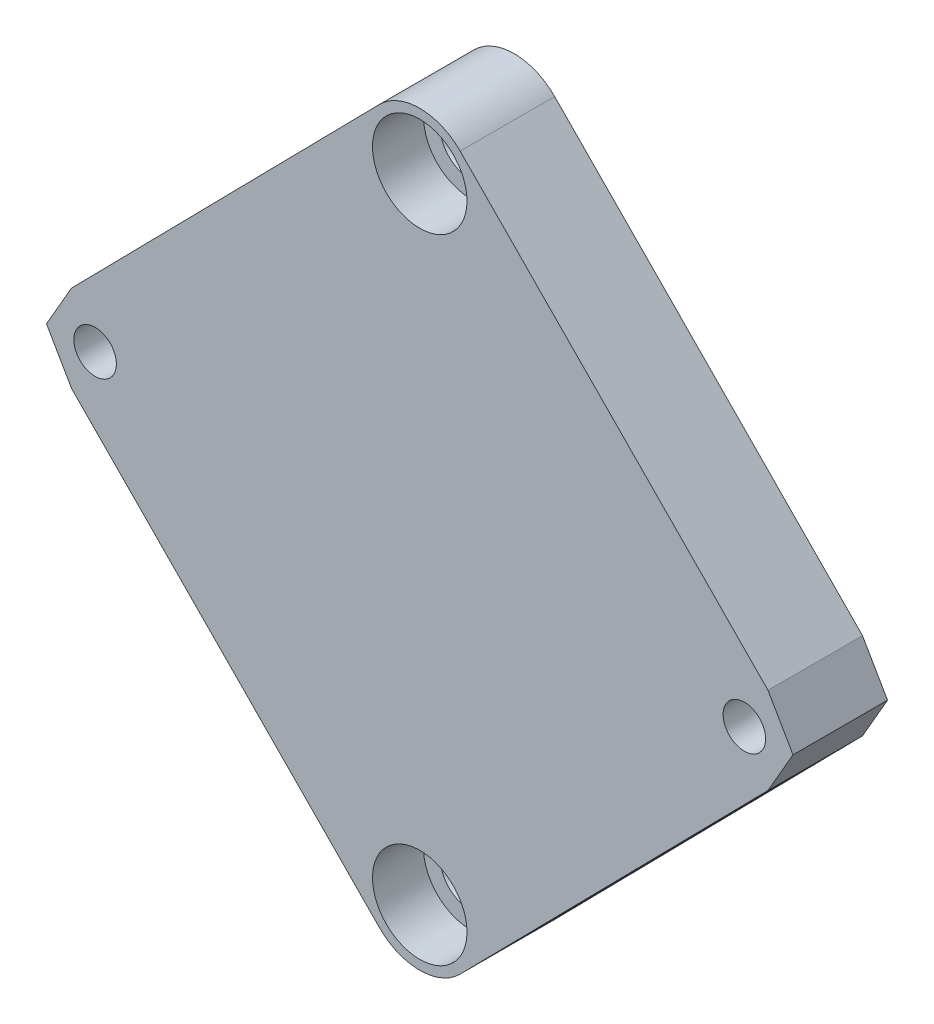
SolidWorks part; units mm, degrees
ref_plane "Top" through (0, 0, 0) normal (0, 0, 1) x (1, 0, 0)
ref_plane "Front" through (0, 0, 0) normal (0, 1, 0) x (1, 0, 0)
ref_plane "Right" through (0, 0, 0) normal (1, 0, 0) x (0, 0, -1)
sketch "Sketch1" plane through (0, 0, 0) normal (0, 0, 1) x (1, 0, 0)
  line L1 (0, 0) -> (79, 0)
  line L2 (0, 0) -> (0, 87)
  line L3 (0, 87) -> (79, 87)
  line L4 (79, 0) -> (79, 87)
  dimension "D1" = 79
  dimension "D2" = 87
extrude "Boss-Extrude1" add sketch "Sketch1" along normal blind 10
sketch "Sketch4" plane through (0, 0, 10) normal (0, 0, 1) x (1, 0, 0)
  line L0 (5.15, 43.5) -> (73.85, 43.5)
  line L2 (79, 0) -> (79, 87) construction
  line L5 (79, 87) -> (0, 87) construction
  point P2 (39.5, 43.5)
  dimension "D1" = 68.7
  dimension "D2" = 39.5
  dimension "D3" = 43.5
hole_wizard "M4 Clearance Hole1" positions "Sketch5" profile "Sketch6" hole size "M4" standard "DIN" end condition through all
sketch "Sketch5" plane through (0, 0, 10) normal (0, 0, 1) x (1, 0, 0)
  point P0 (5.15, 43.5)
  point P3 (73.85, 43.5)
sketch "Sketch6" plane through (5.15, 43.5, 10) normal (1, 0, 0) x (0, -1, 0)
  line L0 (0, 0) -> (0, 10)
  line L1 (0, 10) -> (2.25, 10)
  line L2 (2.25, 10) -> (2.25, 0)
  line L5 (2.25, 0) -> (0, 0)
  line L11 (0, -6.35) -> (0, 107.95) construction
  dimension "Thru Hole Dia." = 4.5
  dimension "Thru Hole Depth" = 10
sketch "Sketch11" plane through (0, 0, 0) normal (0, 0, -1) x (-1, 0, 0)
  line L0 (-79, 87) -> (0, 87) construction
  line L1 (-69.6353, 43.5) -> (-71.7427, 47.15)
  line L2 (-71.7427, 47.15) -> (-75.9573, 47.15)
  line L3 (-75.9573, 47.15) -> (-78.0647, 43.5)
  line L4 (-78.0647, 43.5) -> (-75.9573, 39.85)
  line L5 (-75.9573, 39.85) -> (-71.7427, 39.85)
  line L6 (-71.7427, 39.85) -> (-69.6353, 43.5)
  line L7 (-9.3647, 43.5) -> (-7.2573, 39.85)
  line L8 (-7.2573, 39.85) -> (-3.0427, 39.85)
  line L9 (-3.0427, 39.85) -> (-0.9353, 43.5)
  line L10 (-0.9353, 43.5) -> (-3.0427, 47.15)
  line L11 (-3.0427, 47.15) -> (-7.2573, 47.15)
  line L12 (-7.2573, 47.15) -> (-9.3647, 43.5)
  circle A0 centre (-73.85, 43.5) radius 3.65 construction
  circle A1 centre (-5.15, 43.5) radius 3.65 construction
  dimension "D1" = 7.3
  dimension "D2" = 7.3
extrude "Cut-Extrude3" cut sketch "Sketch11" against normal blind 3.5
sketch "Sketch12" plane through (0, 0, 10) normal (0, 0, -1) x (-1, 0, 0)
  line L0 (-39.5, 77) -> (-39.5, 10)
  line L1 (-79, 0) -> (-79, 87) construction
  line L3 (-79, 87) -> (0, 87) construction
  dimension "D1" = 39.5
  dimension "D2" = 67
  dimension "D3" = 10
hole_wizard "CBORE for M5 Socket Head Cap Screw1" positions "Sketch15" profile "Sketch16" counterbore size "M5" standard "DIN" end condition through all
sketch "Sketch15" plane through (0, 0, 10) normal (0, 0, 1) x (1, 0, 0)
  point P0 (39.5, 77)
  point P3 (39.5, 10)
sketch "Sketch16" plane through (39.5, 77, 10) normal (1, 0, 0) x (0, -1, 0)
  line L0 (0, 0) -> (0, 10)
  line L1 (0, 10) -> (2.75, 10)
  line L3 (2.75, 10) -> (2.75, 5.4)
  line L4 (2.75, 5.4) -> (5, 5.4)
  line L5 (5, 5.4) -> (5, 0)
  line L7 (5, 0) -> (0, 0)
  line L11 (0, -6.35) -> (0, 107.95) construction
  dimension "Thru Hole Dia." = 5.5
  dimension "Thru Hole Depth" = 10
  dimension "C'Bore Dia." = 10
  dimension "C'Bore Depth" = 5.4
sketch "Sketch17" plane through (0, 0, 0) normal (0, 0, -1) x (-1, 0, 0)
  line L0 (-76.3481, 48.0932) -> (-43.7776, 81.2074)
  line L2 (-35.2224, 81.2074) -> (-2.6519, 48.0932)
  line L4 (-76.3481, 38.9068) -> (-43.7776, 5.7926)
  line L5 (-35.2224, 5.7926) -> (-2.6519, 38.9068)
  line L14 (-2.6519, 38.9068) -> (0, 43.5)
  line L15 (0, 87) -> (0, 0) construction
  line L16 (0, 43.5) -> (-2.6519, 48.0932)
  line L17 (-0.9353, 43.5) -> (-3.0427, 47.15) construction
  line L18 (-3.0427, 39.85) -> (-0.9353, 43.5) construction
  line L20 (-76.3481, 48.0932) -> (-79, 43.5)
  line L21 (-79, 0) -> (-79, 87) construction
  line L22 (-79, 43.5) -> (-76.3481, 38.9068)
  line L23 (-78.0647, 43.5) -> (-75.9573, 39.85) construction
  line L24 (-75.9573, 47.15) -> (-78.0647, 43.5) construction
  line L25 (-125.188, 43.5) -> (-108.4403, 14.492)
  line L26 (-108.4403, 14.492) -> (-72.295, -22.2566)
  line L27 (-6.705, -22.2566) -> (29.4403, 14.492)
  line L28 (29.4403, 14.492) -> (46.188, 43.5)
  line L29 (46.188, 43.5) -> (29.4403, 72.508)
  line L30 (-6.705, 109.2566) -> (29.4403, 72.508)
  line L31 (-108.4403, 72.508) -> (-72.295, 109.2566)
  line L32 (-108.4403, 72.508) -> (-125.188, 43.5)
  arc A0 (-43.7776, 81.2074) -> (-35.2224, 81.2074) centre (-39.5, 77) cw
  arc A1 (-43.7776, 5.7926) -> (-35.2224, 5.7926) centre (-39.5, 10) ccw
  arc A4 (-72.295, -22.2566) -> (-6.705, -22.2566) centre (-39.5, 10) ccw
  arc A5 (-72.295, 109.2566) -> (-6.705, 109.2566) centre (-39.5, 77) cw
  dimension "D2" = 6
  dimension "D4" = 6
  dimension "D1" = 0.94
  dimension "D3" = 0.94
  dimension "D5" = 0.94
  dimension "D6" = 0.94
  dimension "D7" = 40
extrude "Cut-Extrude4" cut sketch "Sketch17" against normal blind 10
chamfer "Chamfer2" distance 0.5 angle 45 2 edges at (42.25, 10, 4.6) (42.25, 77, 4.6)
ref_plane "Plane1" through (0, 45.75, 0) normal (0, -1, 0) x (-1, 0, 0)
ref_axis "Axis1" through (39.5, 77, -10.3065) along (0, 0, 1)
ref_axis "Axis2" through (39.5, 10, 0.5) along (0, 0, 1)
ref_plane "Plane2" through (39.5, 0, 0) normal (-1, 0, 0) x (0, 0, 1)
